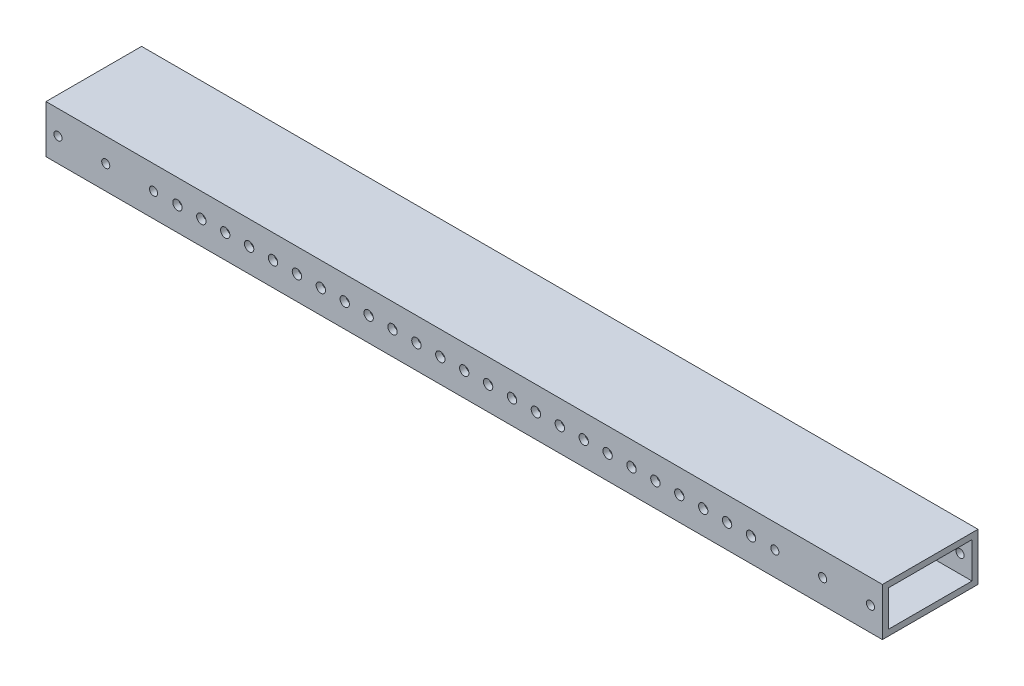
SolidWorks part; units mm, degrees
material "6061-T6 (SS)"
ref_plane "Front Plane" through (0, 0, 0) normal (0, 0, 1) x (1, 0, 0)
ref_plane "Top Plane" through (0, 0, 0) normal (0, 1, 0) x (1, 0, 0)
ref_plane "Right Plane" through (0, 0, 0) normal (1, 0, 0) x (0, 0, -1)
sketch "Sketch1" plane through (0, 0, 0) normal (1, 0, 0) x (0, 0, -1)
  line L1 (0, 0) -> (50.8, 0)
  line L2 (0, 0) -> (0, 25.4)
  line L3 (0, 25.4) -> (50.8, 25.4)
  line L4 (50.8, 0) -> (50.8, 25.4)
  dimension "D1" = 50.8
  dimension "D2" = 25.4
extrude "Boss-Extrude1" add sketch "Sketch1" along normal mid plane 444.5
shell "Shell1" thickness 3.175 removed face at (222.25, 12.7, -25.4) removed face at (-222.25, 12.7, -25.4)
sketch "Sketch2" plane through (0, 0, 0) normal (0, 0, 1) x (1, 0, 0)
  line L0 (-222.25, 25.4) -> (-222.25, 0) construction
  line L1 (222.25, 0) -> (-222.25, 0) construction
  circle A0 centre (-215.9, 12.7) radius 2.1527
  circle A1 centre (-190.5, 12.7) radius 2.1527
  circle A2 centre (-165.1, 12.7) radius 2.1527
  dimension "D1" = 4.3053
  dimension "D3" = 25.4
  dimension "D5" = 12.7
  dimension "D2" = 25.4
  dimension "D4" = 6.35
extrude "Cut-Extrude1" cut sketch "Sketch2" against normal through all
sketch "Sketch3" plane through (0, 0, 0) normal (0, 0, 1) x (1, 0, 0)
  line L0 (222.25, 25.4) -> (-222.25, 25.4) construction
  line L1 (-222.25, 25.4) -> (-222.25, 0) construction
  circle A0 centre (-152.4, 12.7) radius 2.4892
  dimension "D1" = 4.9784
  dimension "D2" = 12.7
  dimension "D3" = 69.85
extrude "Cut-Extrude2" cut sketch "Sketch3" against normal through all
mirror "Mirror1" about plane through (0, 0, 0) normal (1, 0, 0) of "Cut-Extrude1"
pattern_linear "LPattern1" count 25 spacing 12.7 along (1, 0, 0) of "Cut-Extrude2"
